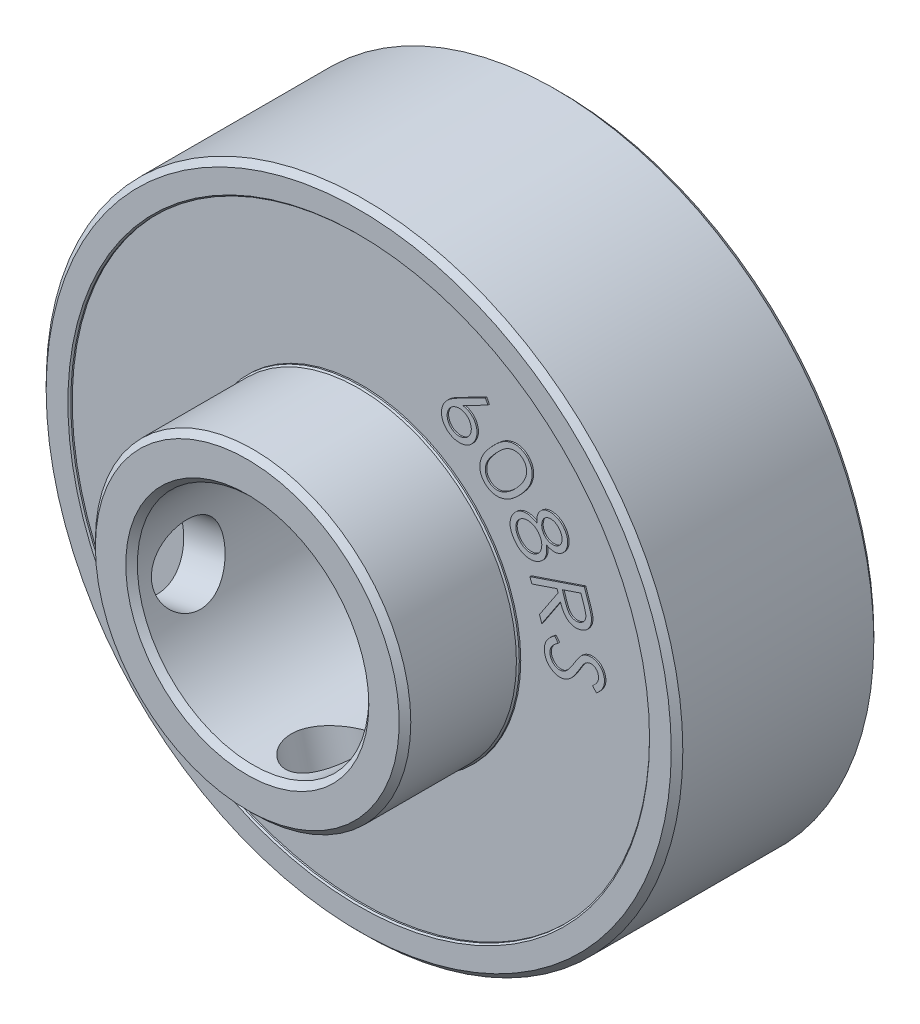
SolidWorks part; units mm, degrees
material "AISI 1020"
ref_plane "Front Plane" through (0, 0, 0) normal (0, 0, 1) x (1, 0, 0)
ref_plane "Top Plane" through (0, 0, 0) normal (0, 1, 0) x (1, 0, 0)
ref_plane "Right Plane" through (0, 0, 0) normal (1, 0, 0) x (0, 0, -1)
sketch "Sketch1" plane through (0, 0, 0) normal (0, 0, 1) x (1, 0, 0)
  circle A0 centre (0, 0) radius 11
  circle A1 centre (0, 0) radius 4
extrude "Boss-Extrude1" add sketch "Sketch1" along normal blind 7
sketch "Sketch2" plane through (0, 0, 7) normal (0, 0, 1) x (1, 0, 0)
  circle A0 centre (0, 0) radius 5.5
  circle A1 centre (0, 0) radius 10
extrude "Cut-Extrude1" cut sketch "Sketch2" against normal blind 0.1
extrude "Cut-Extrude2" cut sketch "Sketch2<2>" against normal blind 0.1 from offset 6.9 offset against normal yes
sketch "Sketch2<2>" plane through (0, 0, 7) normal (0, 0, 1) x (1, 0, 0) same geometry as "Sketch2"
chamfer "Chamfer2" distance 0.05 angle 45 4 edges at (5.5, 0, 7) (10, 0, 7) (10, 0, 0) (5.5, 0, 0)
sketch "Esboço2" plane through (0, 0, 7) normal (0, 0, 1) x (1, 0, 0)
  circle A0 centre (0, 0) radius 5.45
  circle A1 centre (0, 0) radius 4
extrude "Ressalto-extrusão1" add sketch "Esboço2" along normal blind 3.85
sketch "Sketch3" plane through (0, 0, 0.1) normal (0, 0, -1) x (-1, 0, 0)
  circle A0 centre (0, 0) radius 6.5 construction
  text T0 "608RS" font "Century Gothic" height 2
extrude "Boss-Extrude2" add sketch "Sketch3" along normal blind 0.05
chamfer "Chamfer1" distance 0.2 angle 45 5 edges at (4, 0, 0) (11, 0, 7) (11, 0, 0) (5.45, 0, 10.85) (4, 0, 10.85)
sketch "Sketch4" plane through (0, 0, 6.9) normal (0, 0, 1) x (1, 0, 0)
  circle A0 centre (0, 0) radius 6.5 construction
  text T0 "608RS" font "Century Gothic" height 2
extrude "Boss-Extrude3" add sketch "Sketch4" along normal blind 0.05
hole_wizard "Furo roscado de M31" positions "3DSketch1" profile "Esboço3" tap size "M3" standard "ISO"
sketch3d "3DSketch1"
  point P0 (-5.3555, -1.0105, 8.9668)
  point P2 (1.3573, -5.2783, 9.0638)
sketch "Esboço3" plane through (-5.3555, -1.0105, 8.9668) normal (0, 0, 1) x (0.1854, -0.9827, 0)
  line L0 (0, 0) -> (0, 8.2511)
  line L1 (0, 8.2511) -> (1.25, 7.5)
  line L2 (1.25, 7.5) -> (1.25, 0)
  line L5 (1.25, 0) -> (0, 0)
  line L10 (0, 8.2511) -> (-1.25, 7.5) construction
  line L11 (0, -6.35) -> (0, 107.95) construction
  dimension "Tap Drill Dia." = 2.5
  dimension "Tap Drill Depth" = 7.5
  dimension "Drill Angle" = 118
